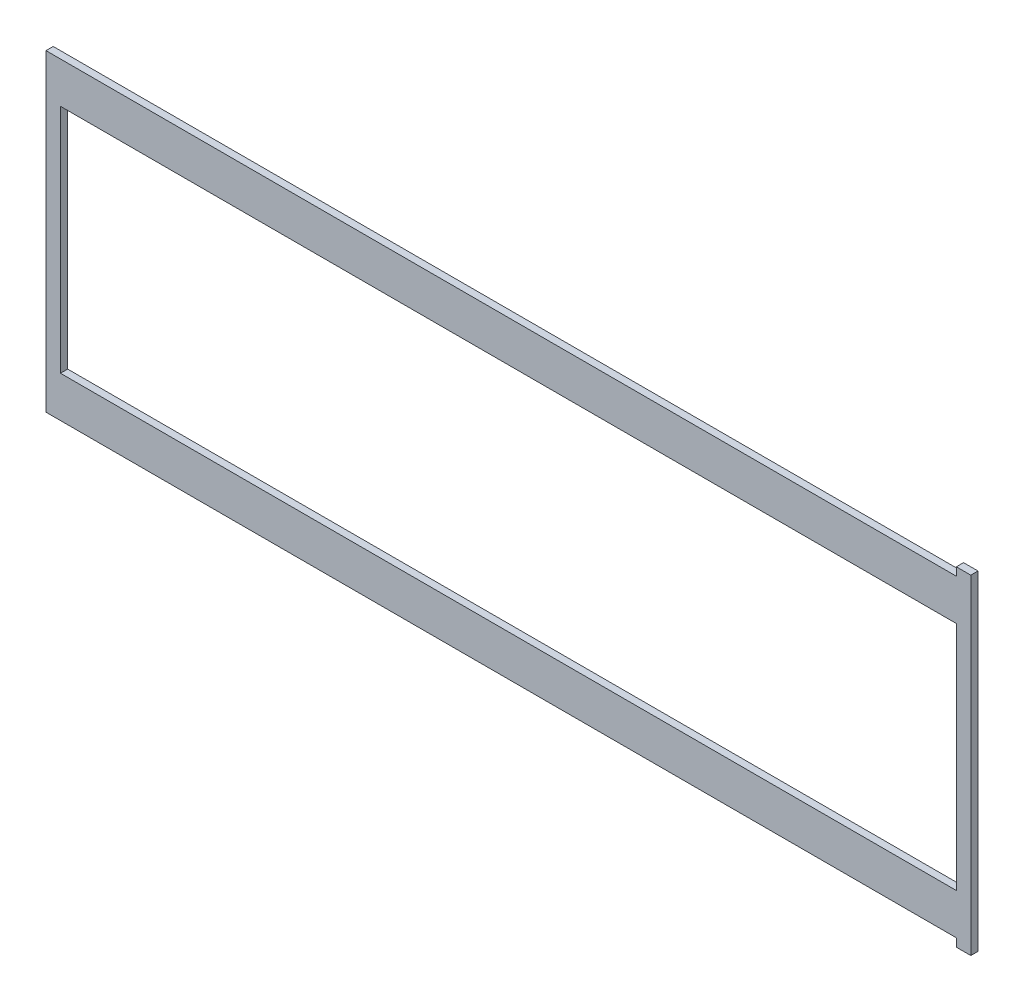
SolidWorks part; units mm, degrees
ref_plane "Front Plane" through (0, 0, 0) normal (0, 0, 1) x (1, 0, 0)
ref_plane "Top Plane" through (0, 0, 0) normal (0, 1, 0) x (1, 0, 0)
ref_plane "Right Plane" through (0, 0, 0) normal (1, 0, 0) x (0, 0, -1)
sketch "Sketch1" plane through (0, 0, 0) normal (0, 0, 1) x (1, 0, 0)
  line L0 (0, 68.8086) -> (406.4, 68.8086) construction
  line L1 (0, 0) -> (400.05, 0)
  line L2 (0, 0) -> (0, 137.6172)
  line L3 (0, 137.6172) -> (400.05, 137.6172)
  line L4 (406.4, 0) -> (406.4, 137.6172)
  line L6 (400.05, 137.6172) -> (400.05, 141.1986)
  line L7 (400.05, 141.1986) -> (406.4, 141.1986)
  line L8 (406.4, 137.6172) -> (406.4, 141.1986)
  line L9 (406.4, 0) -> (406.4, -3.5814)
  line L10 (400.05, -3.5814) -> (406.4, -3.5814)
  line L11 (400.05, 0) -> (400.05, -3.5814)
  line L13 (6.35, 119.6086) -> (400.05, 119.6086)
  line L14 (6.35, 119.6086) -> (6.35, 18.0086)
  line L15 (6.35, 18.0086) -> (400.05, 18.0086)
  line L16 (400.05, 119.6086) -> (400.05, 18.0086)
  point P17 (6.35, 68.8086)
  dimension "D1" = 406.4
  dimension "D2" = 137.6172
  dimension "D3" = 144.78
  dimension "D4" = 6.35
  dimension "D5" = 6.35
  dimension "D6" = 6.35
  dimension "D7" = 101.6
extrude "Boss-Extrude1" add sketch "Sketch1" along normal blind 3.175 contours L0 L2 L1 L11 L10 L4 L16 L15 L14 | L2 L0 L14 L13 L16 L4 L7 L6 L3 region at (203.7696, 125.8644, 0) region at (203.7696, 11.7528, 0)
equation "\"ROADWIDTH\"= 5.418"
equation "\"TABWIDTH\"= 5.7"
equation "\"D2@Sketch1\"=\"ROADWIDTH\""
equation "\"D3@Sketch1\"=\"TABWIDTH\""
